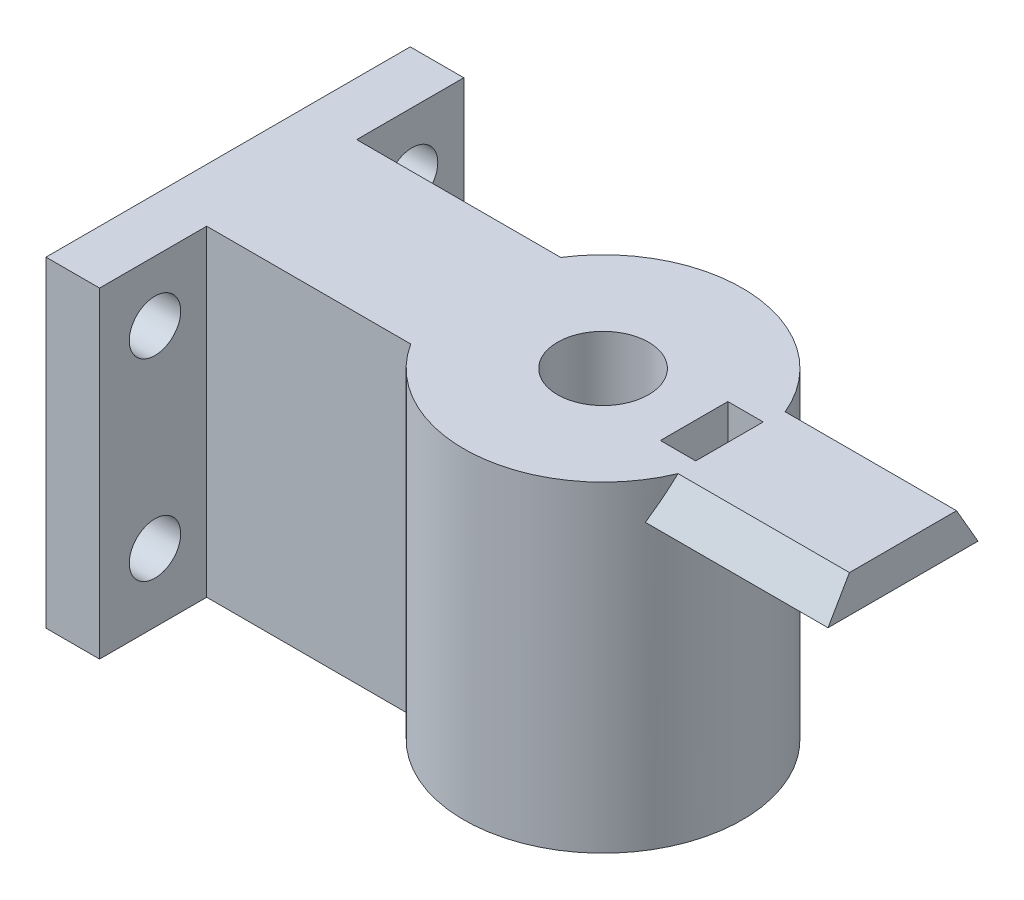
SolidWorks part; units mm, degrees
ref_plane "Front Plane" through (0, 0, 0) normal (0, 0, 1) x (1, 0, 0)
ref_plane "Top Plane" through (0, 0, 0) normal (0, 1, 0) x (1, 0, 0)
ref_plane "Right Plane" through (0, 0, 0) normal (1, 0, 0) x (0, 0, -1)
sketch "Sketch2" plane through (0, 0, 0) normal (0, 1, 0) x (1, 0, 0)
  line L0 (0, 17) -> (0, -17)
  line L1 (0, -17) -> (5, -17)
  line L2 (5, -17) -> (5, -7)
  line L3 (5, -7) -> (24.0455, -7)
  line L4 (24.0455, 7) -> (5, 7)
  line L5 (5, 7) -> (5, 17)
  line L6 (5, 17) -> (0, 17)
  arc A0 (24.0455, 7) -> (24.0455, -7) centre (35, 0) cw
  circle A1 centre (35, 0) radius 4.25
  point P8 (0, 0)
  dimension "D2" = 8.5
  dimension "D6" = 13
  dimension "D1" = 34
  dimension "D3" = 30
  dimension "D4" = 10
  dimension "D5" = 5
extrude "Boss-Extrude1" add sketch "Sketch2" along normal blind 30
sketch "Sketch3" plane through (0, 0, 0) normal (0, -1, 0) x (1, 0, 0)
  circle A0 centre (35, 0) radius 4.25
  circle A1 centre (35, 0) radius 5.25
  circle A2 centre (35, 0) radius 11.25
  circle A3 centre (35, 0) radius 4.25 construction
  circle M12 centre (35, 0) radius 4.25
  dimension "D1" = 10.5
  dimension "D2" = 22.5
extrude "Cut-Extrude1" cut sketch "Sketch3" against normal blind 5 contours A1 M12 | A2 A1 region at (29.8985, 0, 0) region at (24.0682, 0, 0)
extrude "Cut-Extrude2" cut sketch "Sketch3<3>" against normal blind 10.6 from surface contours A1 M12 region at (29.8985, 0, 0) starting at face at (35, 5, -4.25)
sketch "Sketch3<3>" plane through (0, 0, 0) normal (0, -1, 0) x (1, 0, 0) same geometry as "Sketch3"
sketch "Sketch4" plane through (5, 0, 0) normal (1, 0, 0) x (0, 0, -1)
  circle A0 centre (12.1719, 24.3634) radius 2.4
  circle A1 centre (12.1719, 6.3634) radius 2.4
  circle A2 centre (-11.8281, 6.3634) radius 2.4
  circle A3 centre (-11.8281, 24.3634) radius 2.4
  dimension "D1" = 4.8
  dimension "D2" = 24
  dimension "D3" = 18
extrude "Cut-Extrude3" cut sketch "Sketch4" against normal through all
sketch "Sketch5" plane through (0, 5, 0) normal (0, -1, 0) x (1, 0, 0)
  line L0 (27, 0) -> (35, 0) construction
  line L1 (35, 0) -> (43, 0) construction
  line L2 (35, 0) -> (35, 8) construction
  line L3 (35, 0) -> (35, -8) construction
  circle A0 centre (27, 0) radius 1.3
  circle A1 centre (43, 0) radius 1.3
  circle A2 centre (35, 8) radius 1.3
  circle A3 centre (35, -8) radius 1.3
  dimension "D1" = 2.6
  dimension "D3" = 2.6
  dimension "D2" = 8
extrude "Cut-Extrude4" cut sketch "Sketch5" against normal blind 6 contours A2 | A3 region at (35, 5, 8) region at (35, 5, -8)
extrude "Boss-Extrude2" add sketch "Sketch5<3>" along normal blind 3.6 contours A0 | A1 region at (27, 5, 0) region at (43, 5, 0)
sketch "Sketch5<3>" plane through (0, 5, 0) normal (0, -1, 0) x (1, 0, 0) same geometry as "Sketch5"
ref_plane "Plane1" through (48, 0, 0) normal (1, 0, 0) x (0, 0, -1)
sketch "Sketch7" plane through (48, 0, 0) normal (1, 0, 0) x (0, 0, -1)
  line L0 (-5, 30) -> (5, 30)
  line L1 (5, 30) -> (7, 26.5359)
  line L2 (7, 26.5359) -> (-7, 26.5359)
  line L3 (-7, 26.5359) -> (-5, 30)
  line L4 (13, 30) -> (-13, 30) construction
  point P2 (0, 30)
  point P7 (0, 30)
  point P8 (0, 26.5359)
  point P9 (-4.3491, 27.188)
  dimension "D1" = 60
  dimension "D2" = 10
  dimension "D3" = 14
extrude "Boss-Extrude3" add sketch "Sketch7" along normal blind 15 and the other way up to surface other way up to face at (36.0228, 15, 0)
sketch "Sketch9" plane through (48, 0, 0) normal (1, 0, 0) x (0, 0, -1)
  line L0 (0, 30.473) -> (0, 9.5359) construction
  line L1 (3.15, 30.473) -> (3.15, 9.5359)
  line L2 (-3.15, 30.473) -> (-3.15, 9.5359)
  line L3 (-13, 0) -> (13, 0) construction
  line L5 (-7, 26.5359) -> (7, 26.5359) construction
  arc A0 (3.15, 30.473) -> (-3.15, 30.473) centre (0, 30.473) ccw
  arc A1 (-3.15, 9.5359) -> (3.15, 9.5359) centre (0, 9.5359) ccw
  point P3 (0, 20.0044)
  point P10 (0, 0)
  point P11 (0, 30.473)
  dimension "D1" = 6.3
  dimension "D2" = 17
extrude "Cut-Extrude5" cut sketch "Sketch9" against normal blind 3.3 from offset 1.2 offset against normal yes
